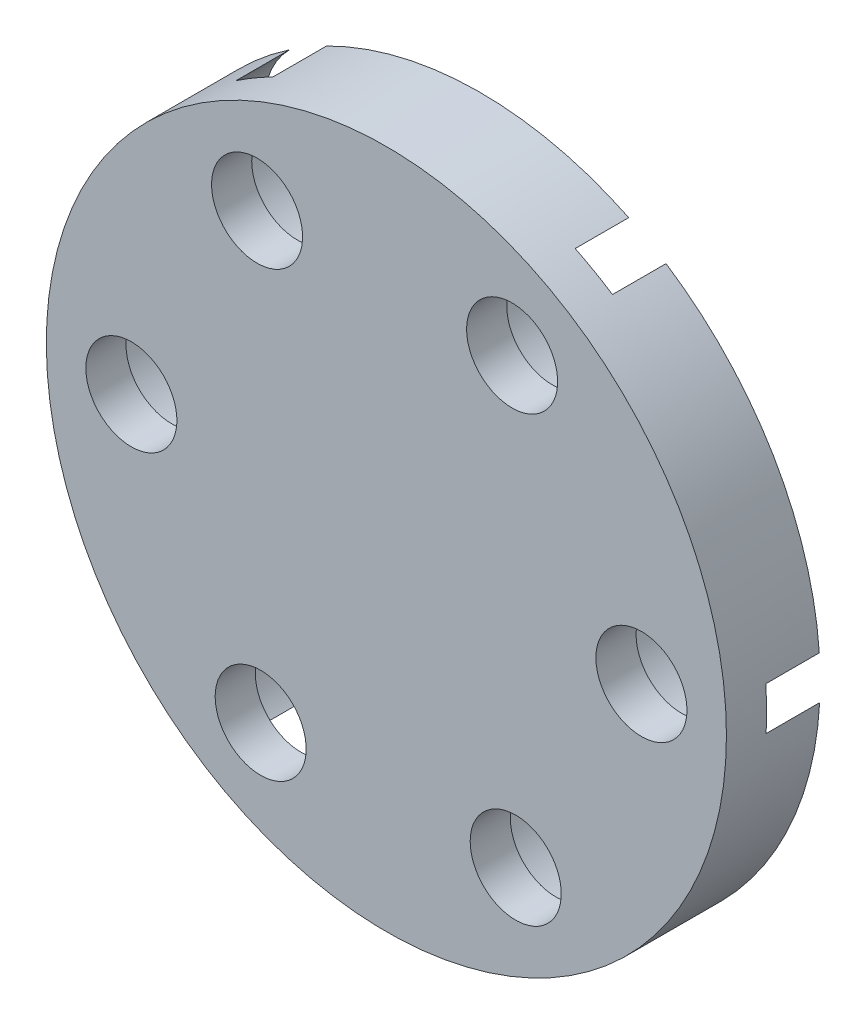
SolidWorks part; units mm, degrees
ref_plane "Front Plane" through (0, 0, 0) normal (0, 0, 1) x (1, 0, 0)
ref_plane "Top Plane" through (0, 0, 0) normal (0, 1, 0) x (1, 0, 0)
ref_plane "Right Plane" through (0, 0, 0) normal (1, 0, 0) x (0, 0, -1)
sketch "Sketch1" plane through (0, 0, 0) normal (0, 0, 1) x (1, 0, 0)
  circle A0 centre (0, 0) radius 12.7
  dimension "D1" = 25.4
extrude "Boss-Extrude1" add sketch "Sketch1" along normal blind 3.5
hole_wizard "CBORE for M3 Cheese Head Screw1" positions "Sketch4" profile "Sketch6" counterbore size "M3" standard "ISO" end condition through all
sketch "Sketch4" plane through (0, 0, 0) normal (0, 0, -1) x (-1, 0, 0)
  point P0 (4.6949, -8.2875)
  point P12 (-4.8297, -8.2097)
  point P13 (-9.5247, 0.0778)
  point P14 (-4.6949, 8.2875)
  point P15 (4.8297, 8.2097)
  point P16 (9.5247, -0.0778)
  dimension "D1" = 9.525
sketch "Sketch6" plane through (-4.6949, -8.2875, 0) normal (1, 0, 0) x (0, 1, 0)
  line L0 (0, 0) -> (0, 3.5)
  line L1 (0, 3.5) -> (1.7, 3.5)
  line L3 (1.7, 3.5) -> (1.7, 2)
  line L4 (1.7, 2) -> (3.25, 2)
  line L5 (3.25, 2) -> (3.25, 0)
  line L7 (3.25, 0) -> (0, 0)
  line L11 (0, -6.35) -> (0, 107.95) construction
  dimension "Thru Hole Dia." = 3.4
  dimension "Thru Hole Depth" = 3.5
  dimension "C'Bore Dia." = 6.5
  dimension "C'Bore Depth" = 2
sketch "Sketch7" plane through (0, 0, 0) normal (0, 0, -1) x (-1, 0, 0)
  circle A0 centre (0, 0) radius 4
  circle A1 centre (0, 0) radius 6.275
  dimension "D1" = 8
extrude "Boss-Extrude2" add sketch "Sketch7" along normal blind 1
chamfer "Chamfer1" distance 0.2 angle 45 1 edges at (-4, 0, -1)
